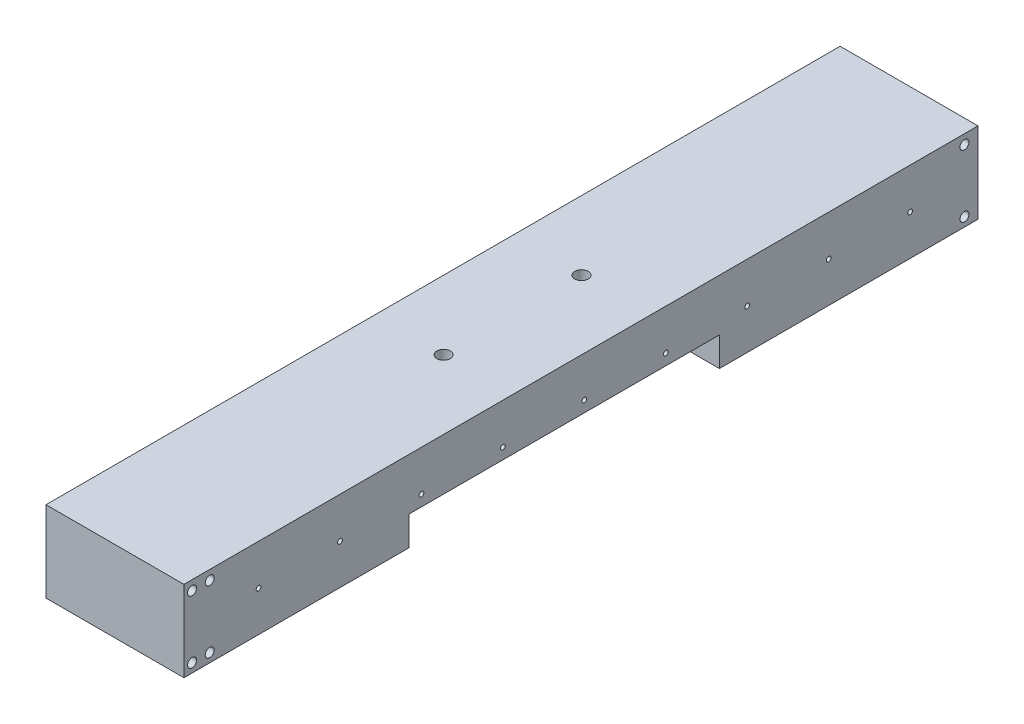
SolidWorks part; units mm, degrees
ref_plane "Front" through (0, 0, 0) normal (0, 0, 1) x (1, 0, 0)
ref_plane "Top" through (0, 0, 0) normal (0, 1, 0) x (1, 0, 0)
ref_plane "Right" through (0, 0, 0) normal (1, 0, 0) x (0, 0, -1)
sketch "Sketch1" plane through (0, 0, 0) normal (0, 0, 1) x (1, 0, 0)
  line L1 (0, 0) -> (101.6, 0)
  line L2 (0, 0) -> (0, 59.6)
  line L3 (0, 59.6) -> (101.6, 59.6)
  line L4 (101.6, 0) -> (101.6, 59.6)
  dimension "D1" = 59.6
  dimension "D2" = 101.6
extrude "Boss-Extrude1" add sketch "Sketch1" along normal blind 585.0001
sketch "Sketch2" plane through (0, 0, 0) normal (-1, 0, 0) x (0, 0, 1)
  line L0 (190.5, 0) -> (190.5, 21.5)
  line L1 (585.0001, 0) -> (0, 0) construction
  line L2 (190.5, 21.5) -> (419.1, 21.5)
  line L3 (419.1, 21.5) -> (419.1, 0)
  line L4 (419.1, 0) -> (190.5, 0)
  line L5 (0, 59.6) -> (0, 0) construction
  dimension "D1" = 190.5
  dimension "D2" = 21.5
  dimension "D3" = 228.6
extrude "Cut-Extrude1" cut sketch "Sketch2" against normal through all
sketch "Sketch5" plane through (0, 0, 0) normal (-1, 0, 0) x (0, 0, 1)
  arc A0 (6.7, 6.6) -> (13.3, 6.6) centre (10, 6.6) ccw construction
  arc A1 (13.3, 6.6) -> (6.7, 6.6) centre (10, 6.6) ccw construction
  arc A2 (6.7, 52.6) -> (13.3, 52.6) centre (10, 52.6) ccw construction
  arc A3 (13.3, 52.6) -> (6.7, 52.6) centre (10, 52.6) ccw construction
  arc A4 (6.7, 6.6) -> (13.3, 6.6) centre (10, 6.6) ccw
  arc A5 (13.3, 6.6) -> (6.7, 6.6) centre (10, 6.6) ccw
  arc A6 (6.7, 52.6) -> (13.3, 52.6) centre (10, 52.6) ccw
  arc A7 (13.3, 52.6) -> (6.7, 52.6) centre (10, 52.6) ccw
  arc A8 (170, 31.35) -> (170, 27.85) centre (170, 29.6) ccw construction
  arc A9 (170, 27.85) -> (170, 31.35) centre (170, 29.6) ccw construction
  arc A10 (110, 27.85) -> (110, 31.35) centre (110, 29.6) ccw construction
  arc A11 (110, 31.35) -> (110, 27.85) centre (110, 29.6) ccw construction
  arc A12 (50, 27.85) -> (50, 31.35) centre (50, 29.6) ccw construction
  arc A13 (50, 31.35) -> (50, 27.85) centre (50, 29.6) ccw construction
  arc A14 (170, 31.35) -> (170, 27.85) centre (170, 29.6) ccw
  arc A15 (170, 27.85) -> (170, 31.35) centre (170, 29.6) ccw
  arc A16 (110, 27.85) -> (110, 31.35) centre (110, 29.6) ccw
  arc A17 (110, 31.35) -> (110, 27.85) centre (110, 29.6) ccw
  arc A18 (50, 27.85) -> (50, 31.35) centre (50, 29.6) ccw
  arc A19 (50, 31.35) -> (50, 27.85) centre (50, 29.6) ccw
  arc A20 (530, 27.85) -> (530, 31.35) centre (530, 29.6) ccw construction
  arc A21 (530, 31.35) -> (530, 27.85) centre (530, 29.6) ccw construction
  arc A22 (470, 27.85) -> (470, 31.35) centre (470, 29.6) ccw construction
  arc A23 (470, 31.35) -> (470, 27.85) centre (470, 29.6) ccw construction
  arc A24 (410, 27.85) -> (410, 31.35) centre (410, 29.6) ccw construction
  arc A25 (410, 31.35) -> (410, 27.85) centre (410, 29.6) ccw construction
  arc A26 (350, 27.85) -> (350, 31.35) centre (350, 29.6) ccw construction
  arc A27 (350, 31.35) -> (350, 27.85) centre (350, 29.6) ccw construction
  arc A28 (290, 27.85) -> (290, 31.35) centre (290, 29.6) ccw construction
  arc A29 (290, 31.35) -> (290, 27.85) centre (290, 29.6) ccw construction
  arc A30 (230, 27.85) -> (230, 31.35) centre (230, 29.6) ccw construction
  arc A31 (230, 31.35) -> (230, 27.85) centre (230, 29.6) ccw construction
  arc A32 (530, 27.85) -> (530, 31.35) centre (530, 29.6) ccw
  arc A33 (530, 31.35) -> (530, 27.85) centre (530, 29.6) ccw
  arc A34 (470, 27.85) -> (470, 31.35) centre (470, 29.6) ccw
  arc A35 (470, 31.35) -> (470, 27.85) centre (470, 29.6) ccw
  arc A36 (410, 27.85) -> (410, 31.35) centre (410, 29.6) ccw
  arc A37 (410, 31.35) -> (410, 27.85) centre (410, 29.6) ccw
  arc A38 (350, 27.85) -> (350, 31.35) centre (350, 29.6) ccw
  arc A39 (350, 31.35) -> (350, 27.85) centre (350, 29.6) ccw
  arc A40 (290, 27.85) -> (290, 31.35) centre (290, 29.6) ccw
  arc A41 (290, 31.35) -> (290, 27.85) centre (290, 29.6) ccw
  arc A42 (230, 27.85) -> (230, 31.35) centre (230, 29.6) ccw
  arc A43 (230, 31.35) -> (230, 27.85) centre (230, 29.6) ccw
  arc A44 (582.3, 6.6) -> (575.7, 6.6) centre (579, 6.6) ccw construction
  arc A45 (575.7, 6.6) -> (582.3, 6.6) centre (579, 6.6) ccw construction
  arc A46 (562.7, 6.6) -> (569.3, 6.6) centre (566, 6.6) ccw construction
  arc A47 (569.3, 6.6) -> (562.7, 6.6) centre (566, 6.6) ccw construction
  arc A48 (575.7, 52.6) -> (582.3, 52.6) centre (579, 52.6) ccw construction
  arc A49 (582.3, 52.6) -> (575.7, 52.6) centre (579, 52.6) ccw construction
  arc A50 (562.7, 52.6) -> (569.3, 52.6) centre (566, 52.6) ccw construction
  arc A51 (569.3, 52.6) -> (562.7, 52.6) centre (566, 52.6) ccw construction
  arc A52 (582.3, 6.6) -> (575.7, 6.6) centre (579, 6.6) ccw
  arc A53 (575.7, 6.6) -> (582.3, 6.6) centre (579, 6.6) ccw
  arc A54 (562.7, 6.6) -> (569.3, 6.6) centre (566, 6.6) ccw
  arc A55 (569.3, 6.6) -> (562.7, 6.6) centre (566, 6.6) ccw
  arc A56 (575.7, 52.6) -> (582.3, 52.6) centre (579, 52.6) ccw
  arc A57 (582.3, 52.6) -> (575.7, 52.6) centre (579, 52.6) ccw
  arc A58 (562.7, 52.6) -> (569.3, 52.6) centre (566, 52.6) ccw
  arc A59 (569.3, 52.6) -> (562.7, 52.6) centre (566, 52.6) ccw
extrude "Cut-Extrude4" cut sketch "Sketch5" along normal blind 6.35 from surface contours A32 A33 | A34 A35 | A36 A37 | A38 A39 | A40 A41 | A42 A43 | A15 A14 | A16 A17 | A18 A19 starting at face at (101.6, 20.275, 298.65)
extrude "Cut-Extrude5" cut sketch "Sketch5<3>" along normal blind 25.4 from surface contours A54 A55 | A52 A53 | A56 A57 | A58 A59 | A4 A5 | A6 A7 region at (0, 6.6, 10) region at (0, 52.6, 10) region at (0, 6.6, 579) region at (0, 6.6, 566) region at (0, 52.6, 579) region at (0, 52.6, 566) starting at face at (101.6, 29.6, 531.75)
sketch "Sketch5<3>" plane through (0, 0, 0) normal (-1, 0, 0) x (0, 0, 1) same geometry as "Sketch5"
sketch "Sketch6" plane through (0, 21.5, 0) normal (0, -1, 0) x (1, 0, 0)
  circle A0 centre (50.8, 342.9) radius 4.9344 construction
  circle A1 centre (50.8, 241.3) radius 4.9344 construction
  circle A2 centre (50.8, 342.9) radius 4.9344
  circle A3 centre (50.8, 241.3) radius 4.9344
extrude "Cut-Extrude6" cut sketch "Sketch6" against normal through all
sketch "Sketch7" plane through (0, 0, 0) normal (-1, 0, 0) x (0, 0, 1)
  arc A0 (525.6376, 34.2067) -> (531.1303, 34.2067) centre (528.384, 35.7999) ccw construction
  arc A1 (525.6376, 37.3931) -> (525.6376, 34.2067) centre (528.384, 35.7999) ccw construction
  arc A2 (531.1303, 37.3931) -> (525.6376, 37.3931) centre (528.384, 35.7999) ccw construction
  arc A3 (531.1303, 34.2067) -> (531.1303, 37.3931) centre (528.384, 35.7999) ccw construction
  arc A4 (525.6376, 34.2067) -> (531.1303, 34.2067) centre (528.384, 35.7999) ccw
  arc A5 (525.6376, 37.3931) -> (525.6376, 34.2067) centre (528.384, 35.7999) ccw
  arc A6 (531.1303, 37.3931) -> (525.6376, 37.3931) centre (528.384, 35.7999) ccw
  arc A7 (531.1303, 34.2067) -> (531.1303, 37.3931) centre (528.384, 35.7999) ccw
  arc A8 (53.5485, 37.3931) -> (48.0559, 37.3931) centre (50.8022, 35.7999) ccw construction
  arc A9 (53.5485, 34.2067) -> (53.5485, 37.3931) centre (50.8022, 35.7999) ccw construction
  arc A10 (48.0559, 34.2067) -> (53.5485, 34.2067) centre (50.8022, 35.7999) ccw construction
  arc A11 (48.0559, 37.3931) -> (48.0559, 34.2067) centre (50.8022, 35.7999) ccw construction
  arc A12 (53.5485, 37.3931) -> (48.0559, 37.3931) centre (50.8022, 35.7999) ccw
  arc A13 (53.5485, 34.2067) -> (53.5485, 37.3931) centre (50.8022, 35.7999) ccw
  arc A14 (48.0559, 34.2067) -> (53.5485, 34.2067) centre (50.8022, 35.7999) ccw
  arc A15 (48.0559, 37.3931) -> (48.0559, 34.2067) centre (50.8022, 35.7999) ccw
extrude "Cut-Extrude7" cut sketch "Sketch7" against normal blind 6.35
